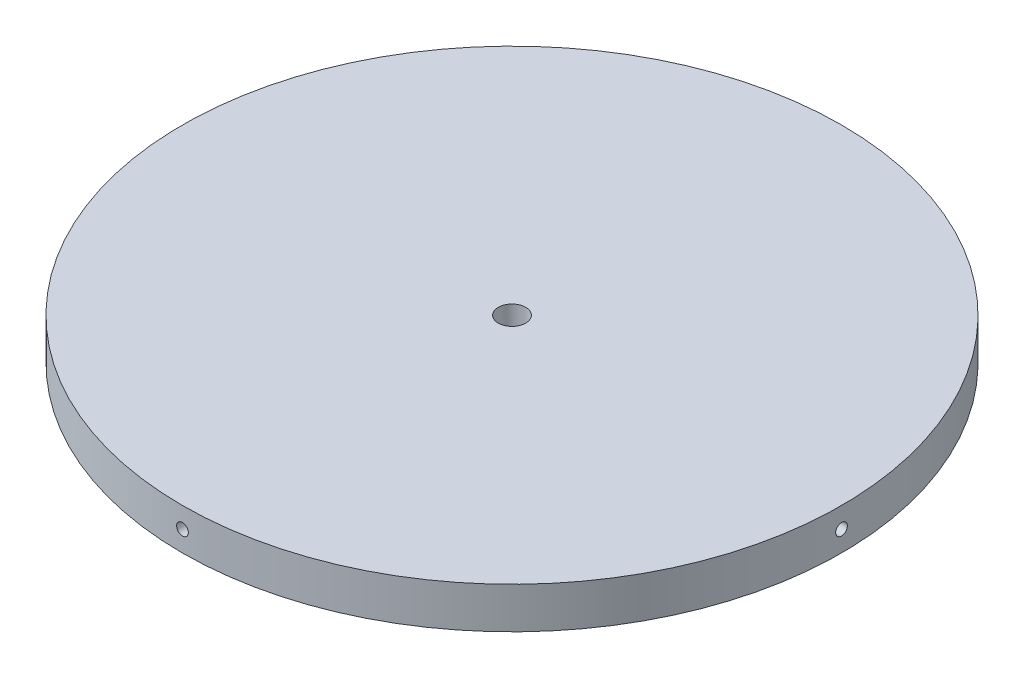
SolidWorks part; units mm, degrees
material "6061-T4 (SS)"
ref_plane "Front Plane" through (0, 0, 0) normal (0, 0, 1) x (1, 0, 0)
ref_plane "Top Plane" through (0, 0, 0) normal (0, 1, 0) x (1, 0, 0)
ref_plane "Right Plane" through (0, 0, 0) normal (1, 0, 0) x (0, 0, -1)
sketch "Sketch1" plane through (0, 0, 0) normal (0, 1, 0) x (1, 0, 0)
  circle A0 centre (0, 0) radius 76.2
  circle A1 centre (0, 0) radius 3.175
  dimension "D1" = 152.4
  dimension "D2" = 6.35
extrude "Boss-Extrude1" add sketch "Sketch1" along normal mid plane 9.525
ref_plane "Plane1" through (0, 0, 76.2) normal (0, 0, 1) x (1, 0, 0)
sketch "Sketch5" plane through (0, 0, 76.2) normal (0, 0, 1) x (1, 0, 0)
  circle A0 centre (0, 0) radius 1.3526
  dimension "D1" = 2.7051
extrude "Cut-Extrude1" cut sketch "Sketch5" against normal blind 19.05
sketch "Sketch14" plane through (0, 0, 0) normal (0, 0, 1) x (1, 0, 0)
  line L0 (0, -5.2723) -> (0, 5.2496)
pattern_circular "CirPattern5" count 4 over 360 about axis through (0, -5.2723, 0) along (0, 1, 0) of "Cut-Extrude1" reverse direction yes
